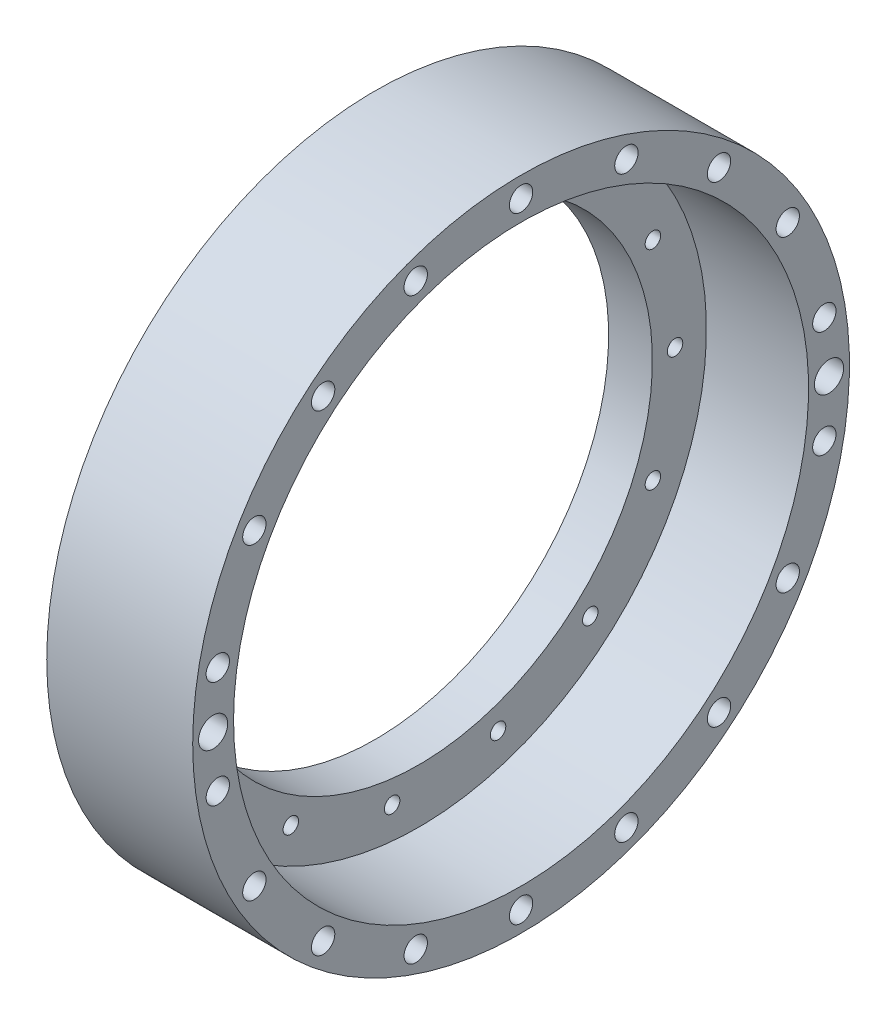
SolidWorks part; units mm, degrees
ref_plane "Front Plane" through (0, 0, 0) normal (0, 0, 1) x (1, 0, 0)
ref_plane "Top Plane" through (0, 0, 0) normal (0, 1, 0) x (1, 0, 0)
ref_plane "Right Plane" through (0, 0, 0) normal (1, 0, 0) x (0, 0, -1)
sketch "Sketch1" plane through (0, 0, 0) normal (0, 0, 1) x (1, 0, 0)
  line L0 (0, 0) -> (146.0265, 0) construction
  line L1 (0, 112.5) -> (0, 80)
  line L2 (0, 80) -> (15, 80)
  line L3 (15, 80) -> (15, 98.5)
  line L4 (15, 98.5) -> (50, 98.5)
  line L5 (50, 98.5) -> (50, 112.5)
  line L6 (50, 112.5) -> (0, 112.5)
  dimension "D1" = 112.5
  dimension "D2" = 80
  dimension "D3" = 15
  dimension "D4" = 50
  dimension "D5" = 98.5
revolve "Revolve1" add sketch "Sketch1" angle 360 about L0
ref_axis "Axis1" through (50, 0, 0) along (-1, 0, 0)
sketch "Sketch3" plane through (50, 0, 0) normal (1, 0, 0) x (0, 0, -1)
  line L0 (0, 0) -> (0, 40.4888) construction
  line L1 (98.5, 0) -> (112.5, 0) construction
  circle A0 centre (0, 0) radius 98.5 construction
  circle A1 centre (0, 0) radius 98.5 construction
  circle A2 centre (0, 0) radius 112.5 construction
  circle A3 centre (105.5, 0) radius 5
  circle A4 centre (-105.5, 0) radius 5
  dimension "D1" = 10
extrude "Cut-Extrude1" cut sketch "Sketch3" against normal through all
sketch "Sketch4" plane through (50, 0, 0) normal (1, 0, 0) x (0, 0, -1)
  line L0 (0, 112.5) -> (0, 98.5) construction
  circle A0 centre (0, 0) radius 112.5 construction
  circle A1 centre (0, 0) radius 98.5 construction
  point P7 (0, 105.5)
hole_wizard "Ø8.0mm Dowel Hole1" positions "3DSketch1" profile "Sketch5" hole size "Ø8.0" standard "ISO" end condition through all
sketch3d "3DSketch1"
  point P0 (50, 105.5, 0)
sketch "Sketch5" plane through (50, 105.5, 0) normal (0, 1, 0) x (0, 0, -1)
  line L0 (0, 0) -> (0, 50)
  line L1 (0, 50) -> (4, 50)
  line L2 (4, 50) -> (4, 0)
  line L5 (4, 0) -> (0, 0)
  line L11 (0, -6.35) -> (0, 107.95) construction
  dimension "Thru Hole Dia." = 8
  dimension "Thru Hole Depth" = 50
pattern_circular "CirPattern1" count 18 over 360 about axis through (50, 0, 0) along (-1, 0, 0) of "Ø8.0mm Dowel Hole1"
sketch "Sketch7" plane through (15, 0, 0) normal (1, 0, 0) x (0, 0, -1)
  circle A0 centre (87.75, 0) radius 2.65
  circle A1 centre (0, 0) radius 87.75 construction
  point P5 (0, 0)
  point P6 (0, 0)
  dimension "D1" = 175.5
  dimension "D2" = 5.3
extrude "Cut-Extrude2" cut sketch "Sketch7" against normal through all
pattern_circular "CirPattern2" count 15 over 360 about axis through (50, 0, 0) along (-1, 0, 0) of "Cut-Extrude2"
